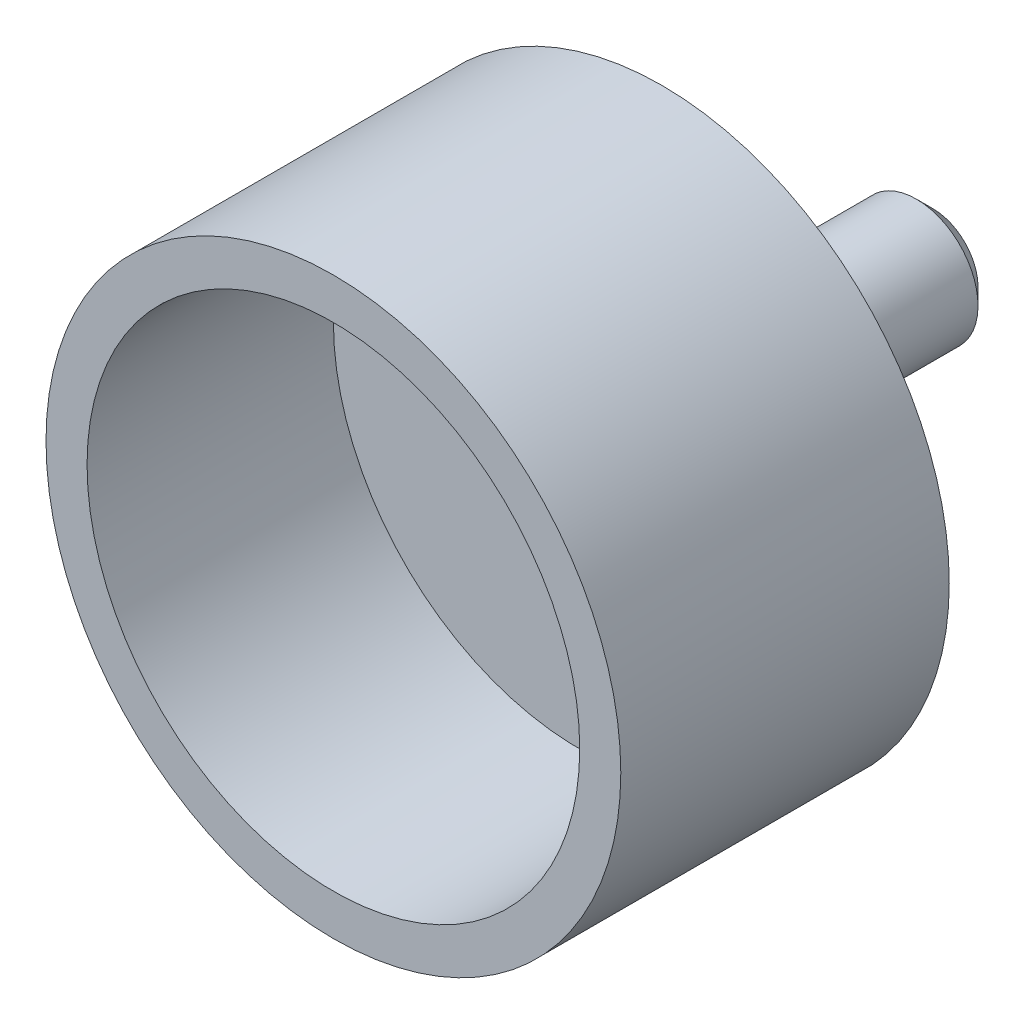
SolidWorks part; units mm, degrees
ref_plane "Front Plane" through (0, 0, 0) normal (0, 0, 1) x (1, 0, 0)
ref_plane "Top Plane" through (0, 0, 0) normal (0, 1, 0) x (1, 0, 0)
ref_plane "Right Plane" through (0, 0, 0) normal (1, 0, 0) x (0, 0, -1)
sketch "Sketch1" plane through (0, 0, 0) normal (0, 0, 1) x (1, 0, 0)
  circle A0 centre (0, 0) radius 35
  dimension "D1" = 70
extrude "Boss-Extrude1" add sketch "Sketch1" along normal blind 35
sketch "Sketch2" plane through (0, 0, 35) normal (0, 0, 1) x (1, 0, 0)
  circle A0 centre (0, 0) radius 35
  dimension "D1" = 70
extrude "Boss-Extrude2" add sketch "Sketch2" along normal blind 5
sketch "Sketch5" plane through (0, 0, 0) normal (0, 0, -1) x (-1, 0, 0)
  circle A0 centre (0, 0) radius 10
  dimension "D1" = 20
ref_plane "Plane1" through (0, 0, -7) normal (0, 0, -1) x (-1, 0, 0)
sketch "Sketch6" plane through (0, 0, -7) normal (0, 0, -1) x (-1, 0, 0)
  circle A0 centre (0, 0) radius 7.5
  dimension "D1" = 15
loft "Loft1" add profiles "Sketch5", "Sketch6" connector at (9.4568, -3.2511, 0) connector at (7.0558, 2.5429, -7)
sketch "Sketch7" plane through (0, 0, -7) normal (0, 0, -1) x (-1, 0, 0)
  circle A1 centre (0, 0) radius 7.5
  circle A2 centre (0, 0) radius 7.5
  dimension "D1" = 0
extrude "Boss-Extrude5" add sketch "Sketch7" along normal blind 26
chamfer "Chamfer1" distance 2 angle 45 1 edges at (-7.5, 0, -33)
sketch "Sketch8" plane through (0, 0, 40) normal (0, 0, 1) x (1, 0, 0)
  circle A0 centre (0, 0) radius 18.7
  dimension "D1" = 37.4
extrude "Cut-Extrude1" cut sketch "Sketch8" against normal blind 22
sketch "Sketch11" plane through (0, 0, 40) normal (0, 0, 1) x (1, 0, 0)
  circle A0 centre (0, 0) radius 30
  dimension "D1" = 60
extrude "Cut-Extrude2" cut sketch "Sketch11" against normal blind 30
